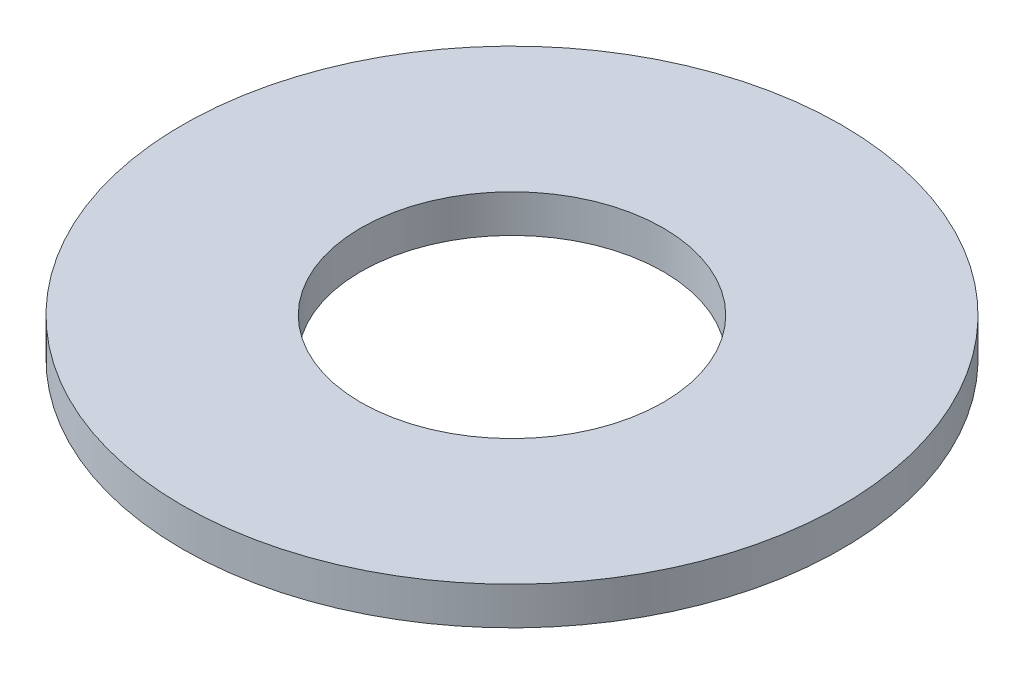
SolidWorks part; units mm, degrees
ref_plane "Front Plane" through (0, 0, 0) normal (0, 0, 1) x (1, 0, 0)
ref_plane "Top Plane" through (0, 0, 0) normal (0, 1, 0) x (1, 0, 0)
ref_plane "Right Plane" through (0, 0, 0) normal (1, 0, 0) x (0, 0, -1)
sketch "Sketch1" plane through (0, 0, 0) normal (0, 1, 0) x (1, 0, 0)
  circle A0 centre (0, 0) radius 9.525
  dimension "OD" = 19.05
extrude "Boss-Extrude1" add sketch "Sketch1" along normal blind 1.0922
sketch "Sketch5" plane through (0, 1.0922, 0) normal (0, 1, 0) x (-1, 0, 0)
  circle A0 centre (0, 0) radius 4.3688
  dimension "ID" = 8.7376
extrude "Cut-Extrude1" cut sketch "Sketch5" against normal through all
ref_axis "Axis1" through (0, -0.0546, 0) along (0, 1, 0)
